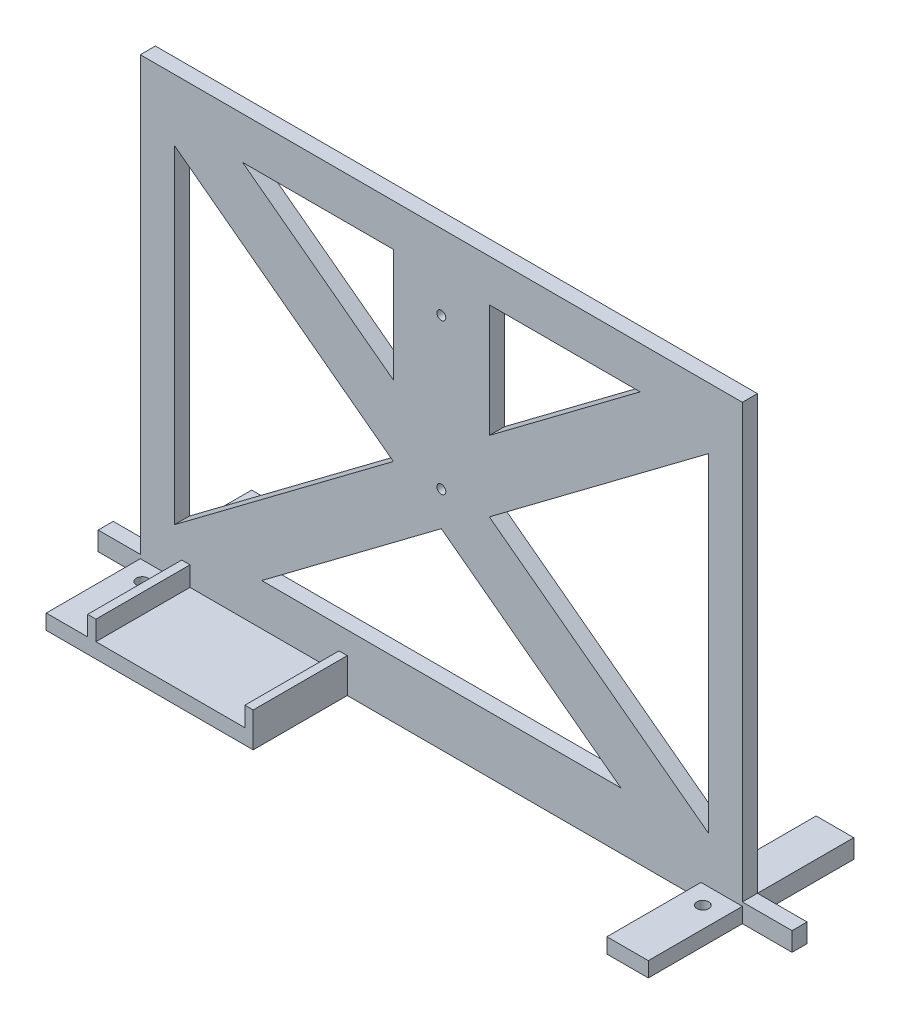
SolidWorks part; units mm, degrees
ref_plane "Front" through (0, 0, 0) normal (0, 0, 1) x (1, 0, 0)
ref_plane "Top" through (0, 0, 0) normal (0, 1, 0) x (1, 0, 0)
ref_plane "Right" through (0, 0, 0) normal (1, 0, 0) x (0, 0, -1)
sketch "Sketch1" plane through (0, 0, 0) normal (0, 0, 1) x (1, 0, 0)
  line L0 (-90.1289, 55.4552) -> (-90.1289, -55.4552)
  line L1 (-101.6, 76.2) -> (101.6, 76.2)
  line L2 (-101.6, 76.2) -> (-101.6, -76.2)
  line L3 (-101.6, -76.2) -> (101.6, -76.2)
  line L4 (101.6, 76.2) -> (101.6, -76.2)
  line L5 (-101.6, 76.2) -> (101.6, -76.2) construction
  line L6 (-101.6, -76.2) -> (101.6, 76.2) construction
  line L7 (0, -55) -> (0, 55) construction
  line L8 (-90.1289, -55.4552) -> (-16.1887, 0)
  line L9 (-16.1887, 0) -> (-90.1289, 55.4552)
  line L10 (55, 0) -> (-55, 0) construction
  line L11 (16.1887, 0) -> (90.1289, 55.4552)
  line L12 (90.1289, -55.4552) -> (16.1887, 0)
  line L13 (90.1289, 55.4552) -> (90.1289, -55.4552)
  line L14 (-16.1887, 61.9912) -> (-16.1887, 23.8125)
  line L15 (-16.1887, 23.8125) -> (-67.0937, 61.9912)
  line L16 (-67.0937, 61.9912) -> (-16.1887, 61.9912)
  line L17 (16.1887, 23.8125) -> (67.0937, 61.9912)
  line L18 (16.1887, 61.9912) -> (16.1887, 23.8125)
  line L19 (67.0937, 61.9912) -> (16.1887, 61.9912)
  line L20 (-60.6282, -57.0175) -> (0, -11.5463)
  line L21 (0, -11.5463) -> (60.6282, -57.0175)
  line L22 (60.6282, -57.0175) -> (-60.6282, -57.0175)
  circle A0 centre (0, 50.8) radius 1.5
  circle A2 centre (0, 0) radius 1.5
  point P0 (0, 0)
  dimension "D3" = 3
  dimension "D4" = 50.8
  dimension "D6" = 19.05
  dimension "D1" = 203.2
  dimension "D2" = 152.4
  dimension "D5" = 25.4
extrude "Boss-Extrude1" add sketch "Sketch1" along normal blind 5.08 contours L4 L1 L2 L3 A2 A0 L19 L17 L18 L9 L8 L0 L11 L13 L12 L15 L16 L14 L21 L22 L20 region at (0, 73.66, 0)
sketch "Sketch2" plane through (0, 0, 5.08) normal (0, 0, 1) x (1, 0, 0)
  line L0 (-101.6, -76.2) -> (101.6, -76.2) construction
  line L1 (-101.6, -76.2) -> (-87.63, -76.2)
  line L2 (-101.6, -76.2) -> (-101.6, -71.12)
  line L3 (-101.6, -71.12) -> (-87.63, -71.12)
  line L4 (-87.63, -76.2) -> (-87.63, -71.12)
  line L5 (0, -55) -> (0, 55) construction
  line L6 (101.6, -71.12) -> (87.63, -71.12)
  line L7 (87.63, -76.2) -> (87.63, -71.12)
  line L8 (101.6, -76.2) -> (87.63, -76.2)
  line L9 (101.6, -76.2) -> (101.6, -71.12)
  line L11 (-87.63, -71.12) -> (-31.75, -71.12)
  line L12 (-87.63, -71.12) -> (-87.63, -76.2)
  line L13 (-87.63, -76.2) -> (-31.75, -76.2)
  line L14 (-31.75, -71.12) -> (-31.75, -76.2)
  line L15 (-87.63, -71.12) -> (-84.836, -71.12)
  line L16 (-87.63, -71.12) -> (-87.63, -64.5258)
  line L17 (-87.63, -64.5258) -> (-84.836, -64.5258)
  line L18 (-84.836, -71.12) -> (-84.836, -64.5258)
  line L19 (-31.75, -71.12) -> (-34.544, -71.12)
  line L20 (-31.75, -71.12) -> (-31.75, -64.5258)
  line L21 (-31.75, -64.5258) -> (-34.544, -64.5258)
  line L22 (-34.544, -71.12) -> (-34.544, -64.5258)
  line M10 (-101.6, -76.2) -> (101.6, -76.2)
  dimension "D1" = 5.08
  dimension "D2" = 55.88
  dimension "D3" = 50.292
  dimension "D4" = 13.97
  dimension "D5" = 31.75
extrude "Boss-Extrude2" add sketch "Sketch2" along normal blind 31.75 contours L4 L3 L2 M10 | L14 L11 L4 M10 | L9 L6 L7 M10 | L16 L15 L18 L17 | L20 L19 L22 L21 region at (-94.615, -73.66, 5.08) region at (94.615, -73.66, 5.08) region at (-59.69, -73.66, 5.08)
sketch "Sketch3" plane through (0, -71.12, 0) normal (0, 1, 0) x (1, 0, 0)
  line L4 (0, -55) -> (0, 55) construction
  line L10 (-101.6, -5.08) -> (-87.63, -5.08) construction
  line L11 (-101.6, -36.83) -> (-101.6, -5.08) construction
  circle A0 centre (-94.615, -11.43) radius 2
  circle A1 centre (94.615, -11.43) radius 2
  dimension "D1" = 4
  dimension "D2" = 6.35
  dimension "D3" = 6.985
extrude "Cut-Extrude1" cut sketch "Sketch3" against normal up to vertex (5.08 mm away) contours A0 | A1 region at (-94.615, -71.12, 11.43) region at (94.615, -71.12, 11.43) up to point (-101.6, -76.2, 36.83)
sketch "Sketch4" plane through (0, 0, 0) normal (0, 0, -1) x (-1, 0, 0)
  line L0 (0, 20.2565) -> (0, -20.2565) construction
  line L1 (-101.6, -76.2) -> (-88.9, -76.2)
  line L2 (-101.6, -76.2) -> (-101.6, -69.85)
  line L3 (-101.6, -69.85) -> (-88.9, -69.85)
  line L4 (-101.6, 76.2) -> (-101.6, -76.2)
  line L5 (-101.6, -76.2) -> (101.6, -76.2)
  line L6 (101.6, -76.2) -> (101.6, 76.2)
  line L7 (101.6, 76.2) -> (-101.6, 76.2)
  line L8 (-101.6, 76.2) -> (-101.6, -76.2)
  line L9 (-101.6, -76.2) -> (101.6, -76.2)
  line L10 (101.6, -76.2) -> (101.6, 76.2)
  line L11 (101.6, 76.2) -> (-101.6, 76.2)
  line L12 (-88.9, -76.2) -> (-88.9, -69.85)
  line L13 (101.6, -69.85) -> (88.9, -69.85)
  line L14 (88.9, -76.2) -> (88.9, -69.85)
  line L15 (101.6, -76.2) -> (88.9, -76.2)
  line L16 (101.6, -76.2) -> (101.6, -69.85)
  dimension "D2" = 12.7
  dimension "D3" = 6.35
  dimension "D1" = 0
extrude "Boss-Extrude3" add sketch "Sketch4" along normal blind 32.512 contours L2 L1 L12 L3 | L16 L13 L14 L15
sketch "Sketch5" plane through (101.6, 0, 0) normal (1, 0, 0) x (0, 0, -1)
  line L1 (0, -69.85) -> (-5.08, -69.85)
  line L2 (0, -69.85) -> (0, -76.2)
  line L3 (0, -76.2) -> (-5.08, -76.2)
  line L4 (-5.08, -69.85) -> (-5.08, -76.2)
extrude "Boss-Extrude4" add sketch "Sketch5" along normal blind 16.764
sketch "Sketch6" plane through (-101.6, 0, 0) normal (-1, 0, 0) x (0, 0, 1)
  line L1 (0, -69.85) -> (5.08, -69.85)
  line L2 (0, -69.85) -> (0, -76.2)
  line L3 (0, -76.2) -> (5.08, -76.2)
  line L4 (5.08, -69.85) -> (5.08, -76.2)
extrude "Boss-Extrude5" add sketch "Sketch6" along normal blind 14.224
